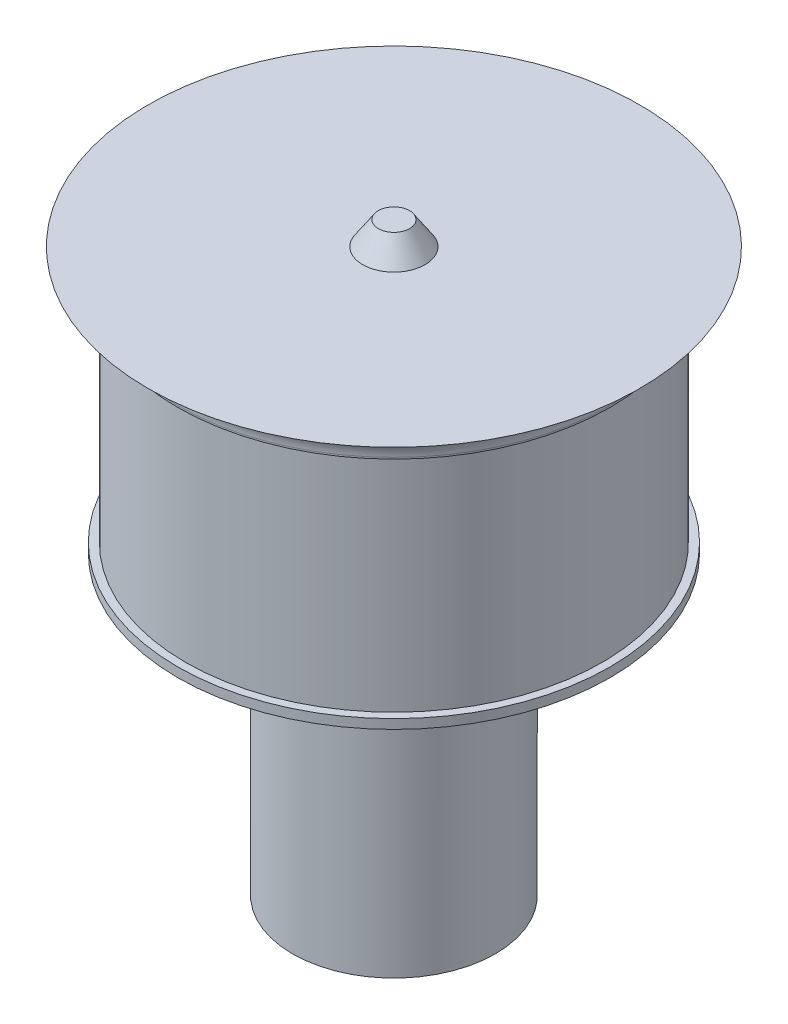
SolidWorks part; units mm, degrees
ref_plane "前视基准面" through (0, 0, 0) normal (0, 0, 1) x (1, 0, 0)
ref_plane "上视基准面" through (0, 0, 0) normal (0, 1, 0) x (1, 0, 0)
ref_plane "右视基准面" through (0, 0, 0) normal (1, 0, 0) x (0, 0, -1)
sketch "草图1" plane through (0, 0, 0) normal (0, 1, 0) x (1, 0, 0)
  circle A0 centre (0, 0) radius 26.7
  dimension "D1" = 53.4
extrude "凸台-拉伸1" add sketch "草图1" along normal blind 28.8
sketch "草图2" plane through (0, 0, 0) normal (0, 0, 1) x (1, 0, 0)
  line L0 (0, 37.2541) -> (0, -8.6254) construction
  line L1 (-26.7, 28.8) -> (-27.7, 28.8)
  line L2 (0, 32.8) -> (-31.5, 32.8)
  line L3 (26.7, 28.8) -> (-26.7, 28.8) construction
  line L4 (0, 28.8) -> (-26.7, 28.8)
  line L5 (-27.7, 29) -> (-27.7, 28.8)
  line L6 (-27.7, 29) -> (0, 29)
  line L7 (0, 32.8) -> (0, 28.8)
  arc A0 (-27.7, 29) -> (-31.5, 32.8) centre (-31.5, 29) ccw
  dimension "D3" = 4
  dimension "D1" = 1
  dimension "D2" = 31.5
revolve "旋转1" add sketch "草图2" angle 360 about L0 region at (-13.85, 28.9, 0)
revolve "旋转2" add sketch "草图2<3>" angle 360 about L0 region at (-14.2704, 30.9301, 0)
sketch "草图2<3>" plane through (0, 0, 0) normal (0, 0, 1) x (1, 0, 0) same geometry as "草图2"
sketch "草图3" plane through (0, 0, 0) normal (0, 0, 1) x (1, 0, 0)
  line L0 (-27.7, 0) -> (-26.7, 0)
  line L1 (-27.7, -1.2) -> (0, -1.2)
  line L2 (0, -1.2) -> (0, 0)
  line L3 (-27.7, 0) -> (-27.7, -1.2)
  line L4 (-26.7, 0) -> (0, 0)
  line L6 (0, 9.5326) -> (0, -6.6997) construction
  dimension "D1" = 1
  dimension "D2" = 1.2
revolve "旋转3" add sketch "草图3" angle 360 about L6
sketch "草图4" plane through (0, -1.2, 0) normal (0, -1, 0) x (1, 0, 0)
  circle A0 centre (0, 0) radius 13
  dimension "D1" = 26
extrude "凸台-拉伸2" add sketch "草图4" along normal blind 39
chamfer "倒角1" distance 1 distance2 1.5 1 edges at (0, -40.2, -13) first distance on face at (0, -40.2, -13)
sketch "草图6" plane through (0, 0, 0) normal (0, 0, 1) x (1, 0, 0)
  line L0 (0, 5.7652) -> (0, -8.0912) construction
  line L1 (-13, -1.2) -> (-13, -5.2)
  line L2 (-13, -1.2) -> (-13, -39.2) construction
  line L3 (-13, -5.2) -> (-27.7, -1.2)
  line L4 (-27.7, -1.2) -> (-13, -1.2)
  dimension "D1" = 4
revolve "旋转4" add sketch "草图6" angle 360 about L0
sketch "草图7" plane through (0, 0, 0) normal (0, 0, 1) x (1, 0, 0)
  line L0 (0, -1.9258) -> (0, -8.8481) construction
  line L1 (-13, -5.2) -> (-12, -5.2)
  line L2 (13, -5.2) -> (-13, -5.2) construction
  line L3 (-13, -5.2) -> (-13, -7.2)
  line L4 (-13, -5.2) -> (-13, -39.2) construction
  line L5 (-13, -7.2) -> (-12, -5.2)
  dimension "D1" = 2
  dimension "D2" = 1
revolve "切除-旋转1" cut sketch "草图7" angle 360 about L0
sketch "草图8" plane through (0, 0, 0) normal (0, 0, 1) x (1, 0, 0)
  line L0 (0, 18.8829) -> (0, 39.9897) construction
  line L1 (0, 32.8) -> (0, 35.8)
  line L2 (31.5, 32.8) -> (-31.5, 32.8) construction
  line L3 (0, 35.8) -> (-2, 35.8)
  line L4 (-2, 35.8) -> (-4, 32.8)
  line L5 (-4, 32.8) -> (0, 32.8)
  dimension "D1" = 3
  dimension "D2" = 4
  dimension "D3" = 2
revolve "旋转5" add sketch "草图8" angle 360 about L0
